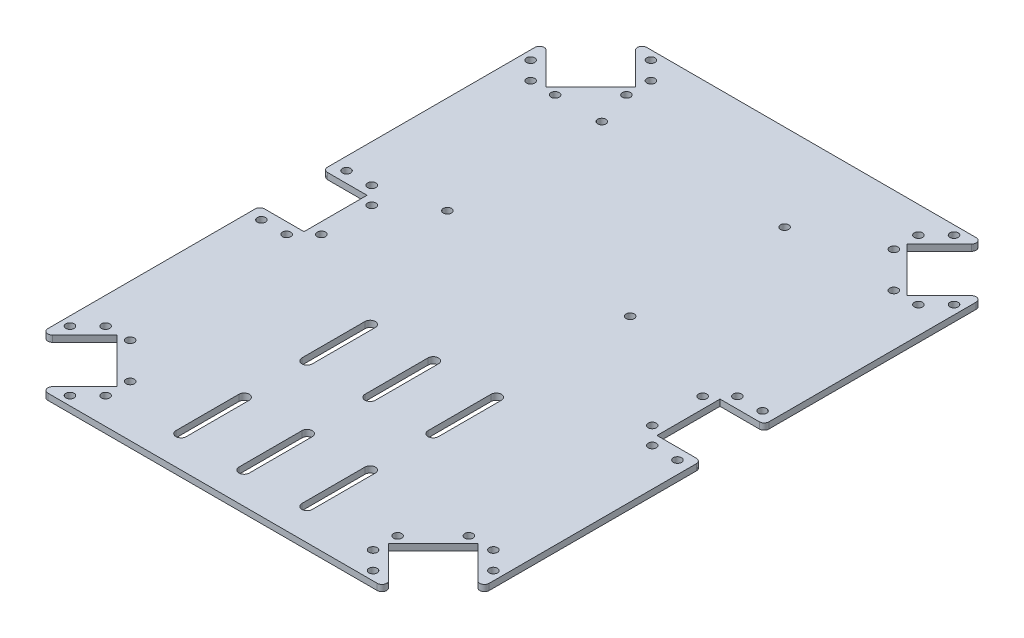
SolidWorks part; units mm, degrees
ref_plane "Front Plane" through (0, 0, 0) normal (0, 0, 1) x (1, 0, 0)
ref_plane "Top Plane" through (0, 0, 0) normal (0, 1, 0) x (1, 0, 0)
ref_plane "Right Plane" through (0, 0, 0) normal (1, 0, 0) x (0, 0, -1)
sketch "Sketch2" plane through (0, 0, 0) normal (0, 1, 0) x (1, 0, 0)
  line L0 (-70, 0) -> (70, 0) construction
  line L1 (-70, 95) -> (70, 95)
  line L2 (-70, 95) -> (-70, -95)
  line L3 (-70, -95) -> (70, -95)
  line L4 (70, 95) -> (70, -95)
  line L5 (70, 95) -> (0, 25) construction
  line L7 (0, 95) -> (0, -95) construction
  line L8 (42.4228, 78.7365) -> (38.5337, 82.6256) construction
  line L9 (38.5337, 82.6256) -> (42.4228, 86.5147) construction
  line L10 (42.4228, 86.5147) -> (48.0797, 92.1716) construction
  line L11 (48.0797, 92.1716) -> (50.9081, 95) construction
  circle A5 centre (42.4228, 78.7365) radius 1.3
  circle A6 centre (42.4228, 86.5147) radius 1.3
  circle A7 centre (48.0797, 92.1716) radius 1.3
  circle A8 centre (66, 13.5) radius 1.3
  circle A9 centre (58, 13.5) radius 1.3
  circle A10 centre (52.5, 8) radius 1.3
  circle A11 centre (52.5, -8) radius 1.3
  circle A12 centre (58, -13.5) radius 1.3
  circle A13 centre (66, -13.5) radius 1.3
  circle A14 centre (67.1716, 73.0797) radius 1.3
  circle A15 centre (61.5147, 67.4228) radius 1.3
  circle A16 centre (53.7365, 67.4228) radius 1.3
  circle A17 centre (67.1716, -73.0797) radius 1.3
  circle A18 centre (61.5147, -67.4228) radius 1.3
  circle A19 centre (53.7365, -67.4228) radius 1.3
  circle A20 centre (48.0797, -92.1716) radius 1.3
  circle A21 centre (42.4228, -86.5147) radius 1.3
  circle A22 centre (42.4228, -78.7365) radius 1.3
  circle A23 centre (-48.0797, 92.1716) radius 1.3
  circle A24 centre (-42.4228, 86.5147) radius 1.3
  circle A25 centre (-42.4228, 78.7365) radius 1.3
  circle A26 centre (-67.1716, 73.0797) radius 1.3
  circle A27 centre (-61.5147, 67.4228) radius 1.3
  circle A28 centre (-53.7365, 67.4228) radius 1.3
  circle A29 centre (-67.1716, -73.0797) radius 1.3
  circle A30 centre (-61.5147, -67.4228) radius 1.3
  circle A31 centre (-53.7365, -67.4228) radius 1.3
  circle A32 centre (-42.4228, -78.7365) radius 1.3
  circle A33 centre (-42.4228, -86.5147) radius 1.3
  circle A34 centre (-48.0797, -92.1716) radius 1.3
  circle A35 centre (-52.5, -8) radius 1.3
  circle A36 centre (-58, -13.5) radius 1.3
  circle A37 centre (-66, -13.5) radius 1.3
  circle A38 centre (-66, 13.5) radius 1.3
  circle A39 centre (-58, 13.5) radius 1.3
  circle A40 centre (-52.5, 8) radius 1.3
  point P0 (0, 0)
  point P27 (0, 0)
  dimension "D6" = 5.5
  dimension "D10" = 8
  dimension "D11" = 5.5
  dimension "D2" = 2.6
  dimension "D3" = 8
  dimension "D4" = 4
  dimension "D5" = 5.5
  dimension "D7" = 45
  dimension "D8" = 140
  dimension "D9" = 190
  dimension "D12" = 5.5
  dimension "D13" = 8
  dimension "D14" = 4
  dimension "D15" = 8
extrude "Boss-Extrude1" add sketch "Sketch2" along normal blind 2
sketch "Sketch3" plane through (0, 2, 0) normal (0, 1, 0) x (1, 0, 0)
  line L0 (0, -95) -> (0, 95) construction
  line L1 (-70, -95) -> (70, -95) construction
  line L2 (70, 95) -> (-70, 95) construction
  line L3 (-70, 0) -> (70, 0) construction
  line L4 (-70, 95) -> (-70, -95) construction
  line L5 (70, -95) -> (70, 95) construction
  line L6 (70, 95) -> (0, 25) construction
  line L7 (70, -10) -> (56, -10)
  line L8 (70, -10) -> (70, 10)
  line L9 (70, 10) -> (56, 10)
  line L10 (56, -10) -> (56, 10)
  line L11 (55.8579, 95) -> (43.1299, 82.2721)
  line L12 (43.1299, 82.2721) -> (57.2721, 68.1299)
  line L13 (57.2721, 68.1299) -> (70, 80.8579)
  line L14 (70, 80.8579) -> (70, 95)
  line L15 (70, 95) -> (55.8579, 95)
  line L16 (70, -80.8579) -> (70, -95)
  line L17 (57.2721, -68.1299) -> (70, -80.8579)
  line L18 (43.1299, -82.2721) -> (57.2721, -68.1299)
  line L19 (55.8579, -95) -> (43.1299, -82.2721)
  line L20 (70, -95) -> (55.8579, -95)
  line L21 (-70, 80.8579) -> (-70, 95)
  line L22 (-57.2721, 68.1299) -> (-70, 80.8579)
  line L23 (-43.1299, 82.2721) -> (-57.2721, 68.1299)
  line L24 (-55.8579, 95) -> (-43.1299, 82.2721)
  line L25 (-70, 95) -> (-55.8579, 95)
  line L26 (-70, 10) -> (-56, 10)
  line L27 (-56, -10) -> (-56, 10)
  line L28 (-70, -10) -> (-56, -10)
  line L29 (-70, -10) -> (-70, 10)
  line L30 (-57.2721, -68.1299) -> (-70, -80.8579)
  line L31 (-43.1299, -82.2721) -> (-57.2721, -68.1299)
  line L32 (-55.8579, -95) -> (-43.1299, -82.2721)
  line L33 (-70, -95) -> (-55.8579, -95)
  line L34 (-70, -80.8579) -> (-70, -95)
  dimension "D1" = 10
  dimension "D2" = 20
  dimension "D3" = 14
  dimension "D4" = 45
  dimension "D5" = 18
  dimension "D6" = 20
  dimension "D7" = 10
extrude "Cut-Extrude1" cut sketch "Sketch3" against normal up to surface (2 mm away) up to face at (0, 0, 0)
fillet "Fillet1" radius 1.5 12 edges at (-70, 1, 10) (-70, 1, -10) (-70, 1, 80.8579) (-55.8579, 1, 95) (55.8579, 1, 95) (70, 1, 80.8579) (70, 1, 10) (70, 1, -10) (70, 1, -80.8579) (55.8579, 1, -95) (-70, 1, -80.8579) (-55.8579, 1, -95)
sketch "Sketch4" plane through (0, 2, 0) normal (0, 1, 0) x (1, 0, 0)
  line L1 (-39, 67.5) -> (19, 67.5) construction
  line L2 (-39, 67.5) -> (-39, 18.5) construction
  line L3 (-39, 18.5) -> (19, 18.5) construction
  line L4 (19, 67.5) -> (19, 18.5) construction
  line L5 (-42.5, 71) -> (42.5, 71) construction
  line L6 (-42.5, 71) -> (-42.5, 15) construction
  line L7 (-42.5, 15) -> (42.5, 15) construction
  line L8 (42.5, 71) -> (42.5, 15) construction
  line L9 (52.2365, 95) -> (-52.2365, 95) construction
  line L10 (-70, 77.2365) -> (-70, 11.5) construction
  circle A0 centre (-39, 67.5) radius 1.3
  circle A1 centre (19, 67.5) radius 1.3
  circle A2 centre (19, 18.5) radius 1.3
  circle A3 centre (-39, 18.5) radius 1.3
  dimension "D1" = 2.6
  dimension "D2" = 58
  dimension "D3" = 85
  dimension "D4" = 56
  dimension "D5" = 49
  dimension "D6" = 3.5
  dimension "D7" = 3.5
  dimension "D8" = 3.5
  dimension "D9" = 24
  dimension "D10" = 27.5
extrude "Cut-Extrude2" cut sketch "Sketch4" against normal up to surface (2 mm away) up to face at (0, 0, 0)
sketch "Sketch5" plane through (0, 2, 0) normal (0, 1, 0) x (1, 0, 0)
  line L0 (-1.65, -65) -> (1.65, -65)
  line L1 (-21.65, -65) -> (-18.35, -65)
  line L2 (-21.65, -65) -> (-21.65, -85)
  line L3 (-21.65, -85) -> (-18.35, -85)
  line L4 (-18.35, -65) -> (-18.35, -85)
  line L5 (-1.65, -65) -> (-1.65, -85)
  line L6 (-1.65, -85) -> (1.65, -85)
  line L7 (1.65, -65) -> (1.65, -85)
  line L8 (18.35, -65) -> (21.65, -65)
  line L9 (18.35, -65) -> (18.35, -85)
  line L10 (18.35, -85) -> (21.65, -85)
  line L11 (21.65, -65) -> (21.65, -85)
  line L12 (-70, -55) -> (70, -55) construction
  line L13 (-70, -11.5) -> (-70, -77.2365) construction
  line L14 (70, -77.2365) -> (70, -11.5) construction
  line L15 (-52.2365, -95) -> (52.2365, -95) construction
  line L16 (0, 95) -> (0, -95) construction
  line L17 (52.2365, 95) -> (-52.2365, 95) construction
  line L18 (21.65, -45) -> (21.65, -25)
  line L19 (18.35, -25) -> (21.65, -25)
  line L20 (18.35, -45) -> (18.35, -25)
  line L21 (18.35, -45) -> (21.65, -45)
  line L22 (1.65, -45) -> (1.65, -25)
  line L23 (-1.65, -25) -> (1.65, -25)
  line L24 (-1.65, -45) -> (-1.65, -25)
  line L25 (-18.35, -45) -> (-18.35, -25)
  line L26 (-21.65, -25) -> (-18.35, -25)
  line L27 (-21.65, -45) -> (-21.65, -25)
  line L28 (-21.65, -45) -> (-18.35, -45)
  line L29 (-1.65, -45) -> (1.65, -45)
  circle A0 centre (-20, -65) radius 1.65
  circle A1 centre (-20, -85) radius 1.65
  circle A2 centre (0, -65) radius 1.65
  circle A3 centre (0, -85) radius 1.65
  circle A4 centre (20, -65) radius 1.65
  circle A5 centre (20, -85) radius 1.65
  circle A6 centre (20, -25) radius 1.65
  circle A7 centre (20, -45) radius 1.65
  circle A8 centre (0, -25) radius 1.65
  circle A9 centre (0, -45) radius 1.65
  circle A10 centre (-20, -25) radius 1.65
  circle A11 centre (-20, -45) radius 1.65
  point P36 (0, 0)
  point P37 (0, -60)
  dimension "D1" = 3.3
  dimension "D2" = 20
  dimension "D4" = 40
  dimension "D5" = 10
  dimension "D3" = 3
extrude "Cut-Extrude3" cut sketch "Sketch5" against normal up to surface (2 mm away) contours L27 A11 L25 A10 | A11 L28 | L20 A7 L18 A6 | L3 A1 | A1 L4 A0 L2 | A10 | A11 | L22 L23 L24 L29 | A8 | A9 | A7 | A6 | A5 | L11 L10 L9 L8 | A4 | L7 L6 L5 L0 | A2 | A3 | A1 | A0 region at (-20, 2, 75) region at (-20, 2, 85.7003) region at (20, 2, 35) region at (-20, 2, 35) region at (-20, 2, 45.7003) up to face at (-39, 0, -17.2)
